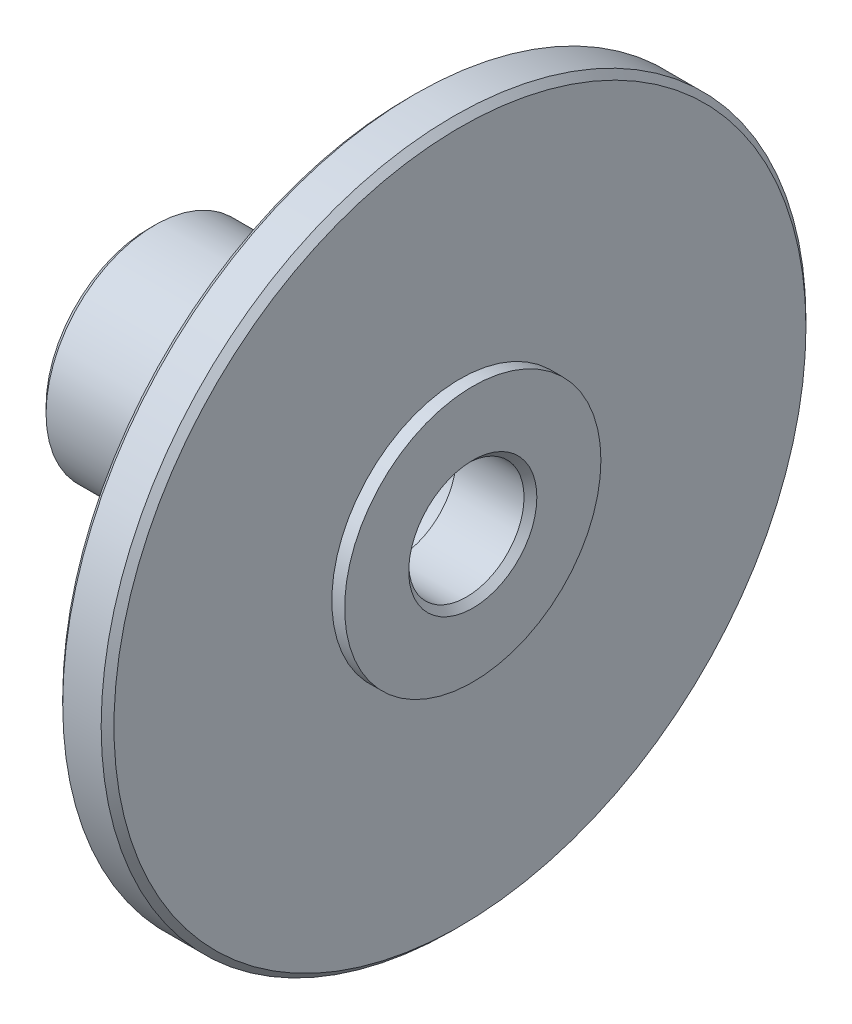
SolidWorks part; units mm, degrees
ref_plane "Front Plane" through (0, 0, 0) normal (0, 0, 1) x (1, 0, 0)
ref_plane "Top Plane" through (0, 0, 0) normal (0, 1, 0) x (1, 0, 0)
ref_plane "Right Plane" through (0, 0, 0) normal (1, 0, 0) x (0, 0, -1)
ref_plane "Plane1" through (0, 0, 216.5) normal (0, 0, -1) x (-1, 0, 0)
sketch "Sketch1" plane through (0, 0, 216.5) normal (0, 0, -1) x (-1, 0, 0)
  line L0 (-184.6, 1) -> (-184.6, -26.5)
  line L1 (-184.6, -26.5) -> (-180.6, -26.5)
  line L2 (-180.6, -26.5) -> (-180.6, 1)
  line L3 (-180.6, 1) -> (-184.6, 1)
  line L4 (-184.6, -26.5) -> (-180.6, -26.5) construction
revolve "Revolve1" add sketch "Sketch1" angle 360 about L4 reverse direction yes
sketch "Sketch2" plane through (184.6, 0, 0) normal (1, 0, 0) x (0, 0, -1)
  circle A0 centre (-216.5, -26.5) radius 10
extrude "Boss-Extrude1" add sketch "Sketch2" along normal blind 1
sketch "Sketch3" plane through (180.6, 0, 0) normal (-1, 0, 0) x (0, 0, 1)
  circle A0 centre (216.5, -26.5) radius 9.5
extrude "Boss-Extrude2" add sketch "Sketch3" along normal blind 8.1
sketch "Sketch4" plane through (172.5, 0, 0) normal (-1, 0, 0) x (0, 0, 1)
  circle A0 centre (216.5, -26.5) radius 8.5
extrude "Boss-Extrude3" add sketch "Sketch4" along normal blind 12.2
sketch "Sketch5" plane through (160.3, 0, 0) normal (-1, 0, 0) x (0, 0, 1)
  line L0 (220.9061, -25.2492) -> (217.7508, -22.0939)
  arc A0 (221.1979, -28.2116) -> (220.9061, -25.2492) centre (221.2376, -26.7121) ccw
  arc A1 (217.7508, -22.0939) -> (214.7884, -21.8021) centre (216.2879, -21.7624) ccw
  arc A2 (214.7884, -21.8021) -> (221.1979, -28.2116) centre (216.5, -26.5) ccw
extrude "Cut-Extrude1" cut sketch "Sketch5" against normal blind 19.5
hole_wizard "Hole1" positions "Sketch7" profile "Sketch6" legacy
sketch "Sketch7" plane through (185.6, 0, 0) normal (1, 0, 0) x (0, 0, -1)
  point P0 (-216.5, -26.5)
sketch "Sketch6" plane through (185.6, -26.5, 216.5) normal (0, 1, 0) x (0, 0, -1)
  line L0 (0, 0) -> (0, 25.3)
  line L1 (0, 25.3) -> (2.5, 25.3)
  line L2 (2.5, 25.3) -> (2.5, 10)
  line L3 (2.5, 10) -> (4.5, 10)
  line L4 (4.5, 10) -> (4.5, 0)
  line L5 (4.5, 0) -> (0, 0)
  line L6 (0, 110) -> (0, -10) construction
  dimension "Diameter" = 5
  dimension "Depth" = 25.3
  dimension "C-Bore Diameter" = 9
  dimension "C-Bore Depth" = 10
chamfer "Chamfer1" distance 0.5 angle 45 4 edges at (184.6, -26.5, 244) (185.6, -26.5, 212) (180.6, -26.5, 244) (160.3, -26.5, 225)
fillet "Fillet1" radius 1 4 edges at (170.05, -25.2492, 220.9061) (170.05, -22.0939, 217.7508) (170.05, -28.2116, 221.1979) (170.05, -21.8021, 214.7884) tangent propagation no
fillet "Fillet2" radius 4 1 edges at (180.6, -26.5, 226) tangent propagation no
